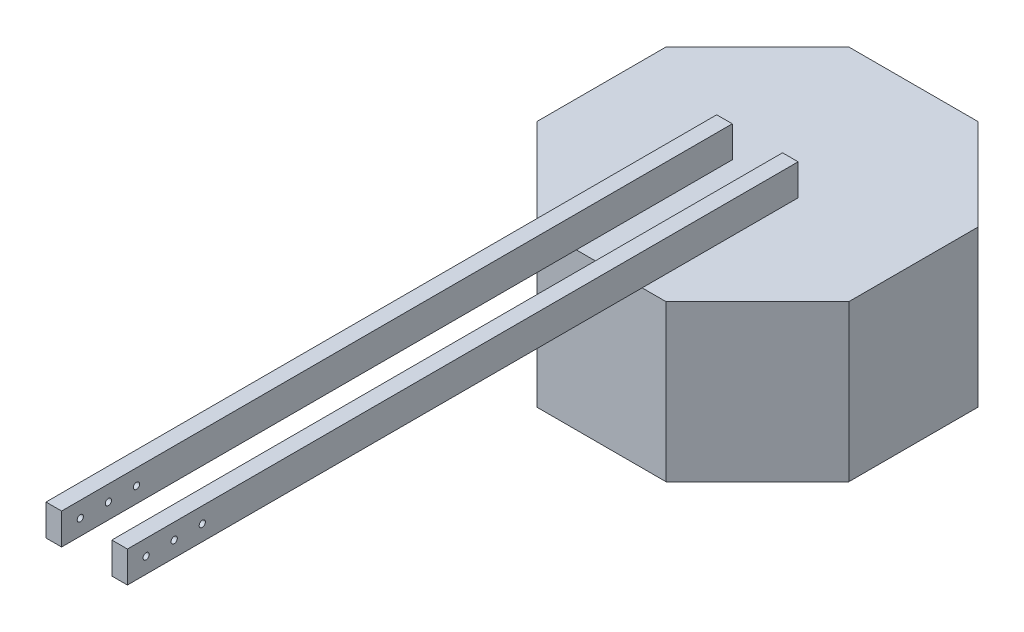
SolidWorks part; units mm, degrees
ref_plane "Front Plane" through (0, 0, 0) normal (0, 0, 1) x (1, 0, 0)
ref_plane "Top Plane" through (0, 0, 0) normal (0, 1, 0) x (1, 0, 0)
ref_plane "Right Plane" through (0, 0, 0) normal (1, 0, 0) x (0, 0, -1)
sketch "Sketch1" plane through (0, 0, 0) normal (0, 1, 0) x (1, 0, 0)
  line L0 (100, -41.4214) -> (100, 41.4214)
  line L1 (41.4214, 100) -> (-41.4214, 100)
  line L2 (-41.4214, 100) -> (-100, 41.4214)
  line L3 (-100, 41.4214) -> (-100, -41.4214)
  line L4 (-100, -41.4214) -> (-41.4214, -100)
  line L5 (-41.4214, -100) -> (41.4214, -100)
  line L6 (41.4214, -100) -> (100, -41.4214)
  line L7 (100, 41.4214) -> (41.4214, 100)
  circle A0 centre (0, 0) radius 100 construction
  dimension "D1" = 200
extrude "Boss-Extrude1" add sketch "Sketch1" along normal blind 100
sketch "Sketch2" plane through (0, 100, 0) normal (0, 1, 0) x (1, 0, 0)
  line L0 (0, 0) -> (0, 210.8552) construction
  line L2 (-26.1, 0) -> (-16.1, 0)
  line L3 (-26.1, 0) -> (-26.1, -430)
  line L4 (-26.1, -430) -> (-16.1, -430)
  line L5 (-16.1, 0) -> (-16.1, -430)
  line L6 (-26.1, 0) -> (-16.1, -430) construction
  line L7 (-26.1, -430) -> (-16.1, 0) construction
  line L8 (26.1, 0) -> (16.1, 0)
  line L9 (16.1, 0) -> (16.1, -430)
  line L10 (26.1, 0) -> (26.1, -430)
  line L11 (26.1, -430) -> (16.1, -430)
  point P3 (-21.1, -215)
  dimension "D1" = 16.1
  dimension "D2" = 10
  dimension "D3" = 430
extrude "Boss-Extrude2" add sketch "Sketch2" along normal blind 20
sketch "Sketch3" plane through (-26.1, 0, 0) normal (-1, 0, 0) x (0, 0, 1)
  line L0 (430, 110) -> (342.8414, 110) construction
  line L1 (430, 120) -> (430, 100) construction
  circle A0 centre (418, 110) radius 2
  circle A1 centre (400, 110) radius 2
  circle A2 centre (382, 110) radius 2
  dimension "D1" = 18
  dimension "D2" = 18
  dimension "D3" = 12
  dimension "D4" = 4
extrude "Cut-Extrude1" cut sketch "Sketch3" against normal through all
